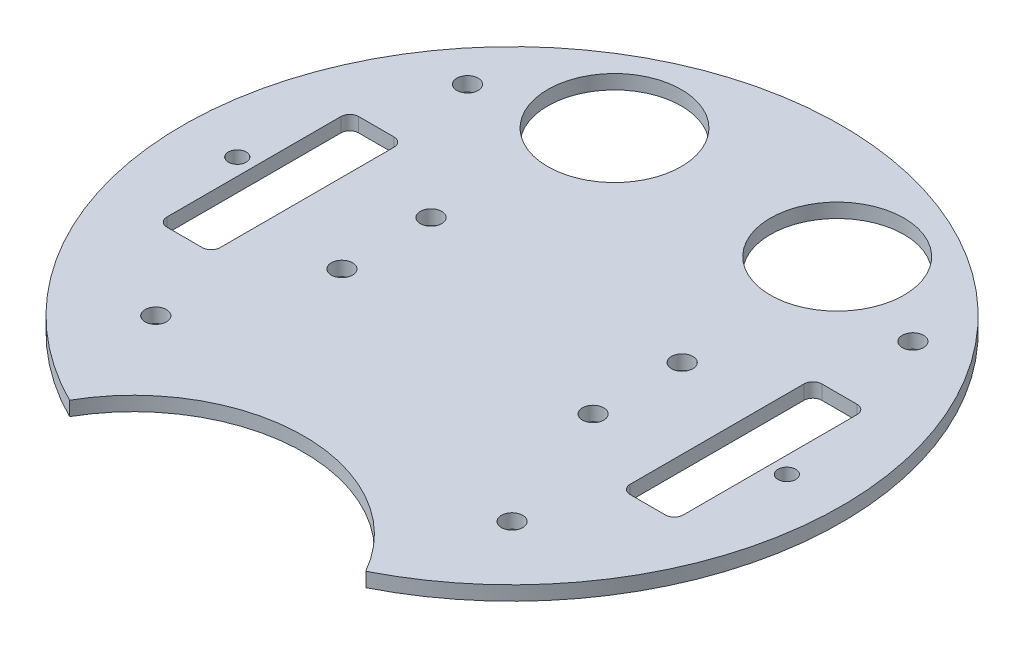
SolidWorks part; units mm, degrees
material "Plain Carbon Steel"
ref_plane "Front Plane" through (0, 0, 0) normal (0, 0, 1) x (1, 0, 0)
ref_plane "Top Plane" through (0, 0, 0) normal (0, 1, 0) x (1, 0, 0)
ref_plane "Right Plane" through (0, 0, 0) normal (1, 0, 0) x (0, 0, -1)
sketch "Sketch1" plane through (0, 0, 0) normal (0, 1, 0) x (1, 0, 0)
  line L0 (0, -85) -> (-33.2575, -66.1055) construction
  line L1 (0, -85) -> (0, 0) construction
  arc A0 (33.2575, -66.1055) -> (-33.2575, -66.1055) centre (0, 0) ccw
  arc A1 (33.2575, -66.1055) -> (-33.2575, -66.1055) centre (0, -85) ccw
  dimension "D1" = 148
  dimension "D2" = 76.5
  dimension "D3" = 85
extrude "Boss-Extrude1" add sketch "Sketch1" along normal blind 3.2
sketch "solenoid placement" plane through (0, 3.2, 0) normal (0, 1, 0) x (1, 0, 0)
  line L0 (0, 0) -> (0, -36) construction
  line L1 (0, -36) -> (0, -46.75) construction
  line L2 (-19, -36) -> (19, -36)
  line L3 (-19, -36) -> (-19, 28)
  line L4 (-19, 28) -> (19, 28)
  line L5 (19, -36) -> (19, 28)
  circle A1 centre (0, 0) radius 74 construction
  arc A2 (33.2575, -66.1055) -> (-33.2575, -66.1055) centre (0, 0) ccw construction
  arc A3 (33.2575, -66.1055) -> (-33.2575, -66.1055) centre (0, -85) ccw construction
  dimension "D1" = 64
  dimension "D2" = 36
  dimension "D4" = 38
sketch "Sketch2" plane through (0, 3.2, 0) normal (0, 1, 0) x (1, 0, 0)
  line L1 (-57.07, 20.6344) -> (-46.91, 20.6344) construction
  line L2 (-57.07, 20.6344) -> (-57.07, -20.6344) construction
  line L3 (-57.07, -20.6344) -> (-46.91, -20.6344) construction
  line L4 (-46.91, 20.6344) -> (-46.91, -20.6344) construction
  line L8 (-57.37, -20.9344) -> (-46.61, -20.9344)
  line L9 (-46.61, 20.9344) -> (-46.61, -20.9344)
  line L10 (-57.37, 20.9344) -> (-46.61, 20.9344)
  line L11 (-57.37, 20.9344) -> (-57.37, -20.9344)
  line L12 (0, 0) -> (0, 74) construction
  line L13 (46.91, 20.6344) -> (46.91, -20.6344) construction
  line L14 (57.07, -20.6344) -> (46.91, -20.6344) construction
  line L15 (57.07, 20.6344) -> (57.07, -20.6344) construction
  line L16 (57.07, 20.6344) -> (46.91, 20.6344) construction
  line L17 (57.37, 20.9344) -> (57.37, -20.9344)
  line L18 (57.37, 20.9344) -> (46.61, 20.9344)
  line L19 (46.61, 20.9344) -> (46.61, -20.9344)
  line L20 (57.37, -20.9344) -> (46.61, -20.9344)
  arc A0 (33.2575, -66.1055) -> (-33.2575, -66.1055) centre (0, 0) ccw construction
extrude "Cut-Extrude1" cut sketch "Sketch2" against normal through all
sketch "Sketch3" plane through (0, 0, 0) normal (0, -1, 0) x (1, 0, 0)
  line L0 (0, 0) -> (0, -74) construction
  circle A0 centre (-61.7, 0) radius 2
  circle A1 centre (-28.2, 10) radius 2.4
  circle A2 centre (-28.2, -10) radius 2.4
  arc A3 (-33.2575, 66.1055) -> (33.2575, 66.1055) centre (0, 0) ccw construction
  circle A4 centre (28.2, -10) radius 2.4
  circle A5 centre (28.2, 10) radius 2.4
  circle A6 centre (61.7, 0) radius 2
  dimension "D1" = 4
  dimension "D2" = 4.8
extrude "Cut-Extrude2" cut sketch "Sketch3" against normal through all
sketch "Sketch4" plane through (0, 3.2, 0) normal (0, 1, 0) x (1, 0, 0)
  line L0 (0, 0) -> (0, 74) construction
  line L1 (0, 48) -> (-25, 48) construction
  circle A0 centre (-25, 48) radius 15
  arc A1 (33.2575, -66.1055) -> (-33.2575, -66.1055) centre (0, 0) ccw construction
  circle A2 centre (25, 48) radius 15
  dimension "D1" = 30
  dimension "D2" = 48
  dimension "D3" = 25
extrude "Cut-Extrude3" cut sketch "Sketch4" against normal through all
sketch "Sketch5" plane through (0, 3.2, 0) normal (0, 1, 0) x (1, 0, 0)
  line L0 (0, 0) -> (0, 74) construction
  line L1 (-55.9558, 21.5201) -> (-48.0242, 21.5201)
  line L2 (-57.9558, 19.5201) -> (-57.9558, -19.5201)
  line L3 (-55.9558, -21.5201) -> (-48.0242, -21.5201)
  line L4 (-46.0242, 19.5201) -> (-46.0242, -19.5201)
  line L5 (46.0242, 19.5201) -> (46.0242, -19.5201)
  line L6 (55.9558, -21.5201) -> (48.0242, -21.5201)
  line L7 (57.9558, 19.5201) -> (57.9558, -19.5201)
  line L8 (55.9558, 21.5201) -> (48.0242, 21.5201)
  arc A0 (-57.9558, -19.5201) -> (-55.9558, -21.5201) centre (-55.9558, -19.5201) ccw
  arc A1 (-48.0242, -21.5201) -> (-46.0242, -19.5201) centre (-48.0242, -19.5201) ccw
  arc A2 (-48.0242, 21.5201) -> (-46.0242, 19.5201) centre (-48.0242, 19.5201) cw
  arc A3 (-55.9558, 21.5201) -> (-57.9558, 19.5201) centre (-55.9558, 19.5201) ccw
  arc A4 (33.2575, -66.1055) -> (-33.2575, -66.1055) centre (0, 0) ccw construction
  arc A5 (55.9558, 21.5201) -> (57.9558, 19.5201) centre (55.9558, 19.5201) cw
  arc A6 (48.0242, 21.5201) -> (46.0242, 19.5201) centre (48.0242, 19.5201) ccw
  arc A7 (48.0242, -21.5201) -> (46.0242, -19.5201) centre (48.0242, -19.5201) cw
  arc A8 (57.9558, -19.5201) -> (55.9558, -21.5201) centre (55.9558, -19.5201) cw
  point P15 (-57.37, 20.9344)
  dimension "D1" = 2
extrude "Cut-Extrude4" cut sketch "Sketch5" against normal through all
sketch "Sketch6" plane through (0, 3.2, 0) normal (0, 1, 0) x (1, 0, 0)
  line L0 (0, 74) -> (0, -46.75) construction
  circle A0 centre (-50, 40) radius 2.4
  circle A1 centre (-40, -40) radius 2.4
  arc A4 (33.2575, -66.1055) -> (-33.2575, -66.1055) centre (0, 0) ccw construction
  arc A5 (33.2575, -66.1055) -> (-33.2575, -66.1055) centre (0, -85) ccw construction
  circle A6 centre (40, -40) radius 2.4
  circle A7 centre (50, 40) radius 2.4
  dimension "D3" = 4.8
  dimension "D1" = 40
  dimension "D2" = 40
  dimension "D4" = 50
  dimension "D5" = 40
extrude "Cut-Extrude5" cut sketch "Sketch6" against normal through all
chamfer "Chamfer1" [suppressed] distance 2 angle 41
equation "\"smallPulleyTeeth\"= 15"
equation "\"largePulleyTeeth\"= 30"
equation "\"eighthThick\"= 2.9mm"
equation "\"sixteenthThick\" = 1.7mm"
equation "\"quarterThick\"=6.0mm"
equation "\"OD\" = 146mm"
equation "\"puckAngle\" = 60.5deg"
equation "\"puckDiam\" = 76.5mm"
equation "\"D2@Sketch1\"=\"puckDiam\""
equation "\"D1@Boss-Extrude1\"=\"eighthThick\""
equation "\"axlePress\" = 5.9mm"
equation "\"press\" = 0.2mm"
equation "\"wheelClear\" = 0.3mm"
equation "\"D1@Sketch2\"=\"wheelClear\""
equation "\"10-32clear\" = 4.8mm"
equation "\"6-32clear\" = 3.3mm"
equation "\"8-32clear\" = 4.0mm"
equation "\"wheelHeight\" = 22mm"
equation "\"D1@Sketch3\"=\"8-32clear\""
equation "\"D2@Sketch3\"=\"10-32clear\""
equation "\"D3@Sketch6\"=\"10-32clear\""
equation "\"puckDist\" = 85mm"
equation "\"4-40clear\" = 3.0mm"
equation "\"wheelWell\" = 65mm"
equation "\"D3@Sketch1\"=\"puckDist\""
